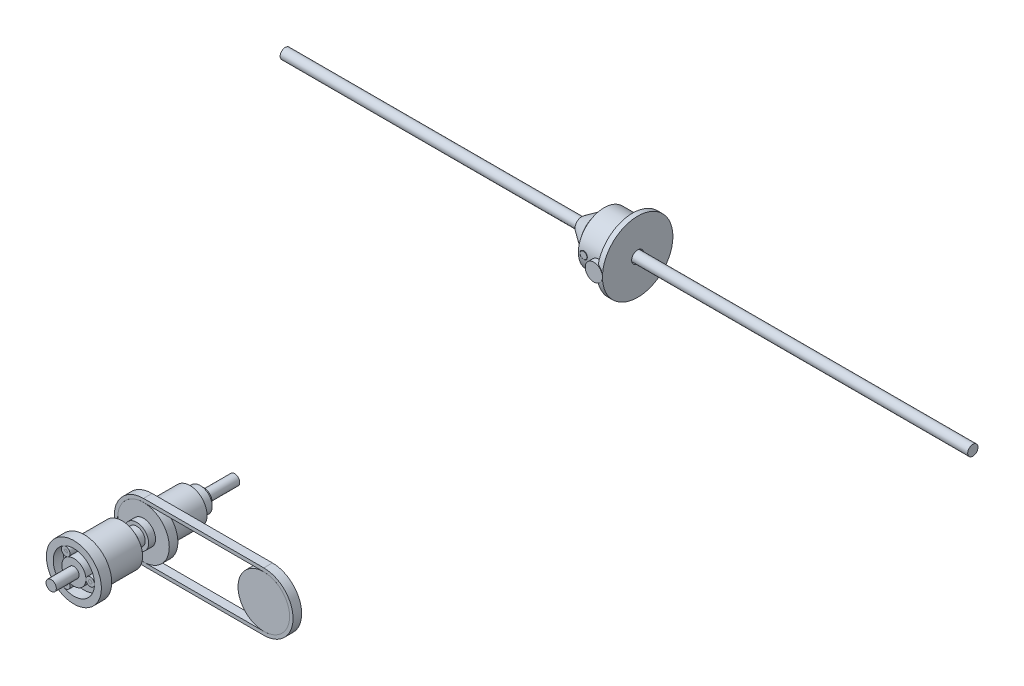
SolidWorks part; units mm, degrees
note: The reader was unsure of these and kept them because the rebuilt part matched: shared geometry of "Sketch14<2>", "Sketch32<3>", "Sketch50<2>", "Sketch52<2>".
other "RD S Gear Inner"
other "RD S Gear Outer"
other "RD L Gear Left"
other "RD L Gear Right"
other "RD Ring Gear"
other "RD Pinion"
other "RD S Gear Inner"
ref_plane "Front Plane" through (0, 0, 0) normal (0, 0, 1) x (1, 0, 0)
ref_plane "Top Plane" through (0, 0, 0) normal (0, 1, 0) x (1, 0, 0)
ref_plane "Right Plane" through (0, 0, 0) normal (1, 0, 0) x (0, 0, -1)
sketch "Top View Layout" plane through (0, 0, 0) normal (0, 1, 0) x (1, 0, 0)
  line L0 (-100, 125) -> (100, 125)
  line L1 (0, 125) -> (0, -125)
  line L2 (-100, -125) -> (100, -125)
  line L3 (0, -15) -> (35, -15) construction
  line L4 (35, -15) -> (35, -125) construction
  line L5 (2.5, 114.75) -> (2.5, 135.25) construction
  line L6 (-2.5, 114.75) -> (2.5, 114.75) construction
  line L7 (-8.75, 127) -> (-2.75, 127) construction
  line L8 (-2.5, 114.75) -> (2.5, 114.75) construction
  line L9 (-2.5, 114.75) -> (-2.5, 116.25) construction
  line L10 (-2.5, 116.25) -> (2.5, 116.25) construction
  line L11 (2.5, 114.75) -> (2.5, 116.25) construction
  line L12 (2.5, 135.25) -> (1, 135.25) construction
  line L13 (2.5, 135.25) -> (2.5, 114.75) construction
  line L14 (2.5, 114.75) -> (1, 114.75) construction
  line L15 (1, 135.25) -> (1, 114.75) construction
  line L16 (-4.25, 128.5) -> (-2.75, 128.5) construction
  line L17 (-4.25, 128.5) -> (-4.25, 121.5) construction
  line L18 (-4.25, 121.5) -> (-2.75, 121.5) construction
  line L19 (-2.75, 128.5) -> (-2.75, 121.5) construction
  line L20 (-4.25, 128.5) -> (-2.75, 121.5) construction
  line L21 (-4.25, 121.5) -> (-2.75, 128.5) construction
  line L22 (-8.75, 128.5) -> (-7.25, 128.5) construction
  line L23 (-8.75, 128.5) -> (-8.75, 121.5) construction
  line L24 (-8.75, 121.5) -> (-7.25, 121.5) construction
  line L25 (-7.25, 128.5) -> (-7.25, 121.5) construction
  line L26 (-8.75, 128.5) -> (-7.25, 121.5) construction
  line L27 (-8.75, 121.5) -> (-7.25, 128.5) construction
  line L28 (-8.75, 123) -> (-2.75, 123) construction
  line L29 (-5.75, 123) -> (-5.75, 120.2863) construction
  line L30 (-5.75, 127) -> (-5.75, 129.2691) construction
  point P8 (0, 114.75)
  point P9 (0, 0)
  point P11 (2.5, 125)
  point P16 (2.5, 125)
  point P19 (0, 114.75)
  point P23 (-3.5, 125)
  point P28 (-8, 125)
  dimension "D1" = 250
  dimension "D2" = 200
  dimension "D3" = 35
  dimension "D4" = 15
  dimension "D5" = 5
  dimension "D6" = 20.5
  dimension "D7" = 1.5
  dimension "D8" = 1.5
  dimension "D9" = 1.5
  dimension "D10" = 7
  dimension "D11" = 3.5
  dimension "D12" = 8
  dimension "D13" = 1.5
  dimension "D14" = 1.5
ref_plane "Left" through (100, 0, 0) normal (-1, 0, 0) x (0, 0, 1)
ref_plane "Right" through (-100, 0, 0) normal (-1, 0, 0) x (0, 0, 1)
sketch "Left Wheels" plane through (100, 0, 0) normal (-1, 0, 0) x (0, 0, 1)
  circle A0 centre (125, 0) radius 25
  circle A1 centre (-125, 0) radius 25
  dimension "D1" = 50
  dimension "D2" = 50
sketch "Right Wheels" plane through (-100, 0, 0) normal (-1, 0, 0) x (0, 0, 1)
  circle A0 centre (-125, 0) radius 25 construction
  circle A1 centre (125, 0) radius 25 construction
  circle A2 centre (-125, 0) radius 25
  circle A3 centre (125, 0) radius 25
ref_plane "Rear Differential Pinion Plane" through (0, 0, -114.75) normal (0, 0, 1) x (1, 0, 0)
sketch "Rear Differential Pinion Profile" plane through (0, 0, -114.75) normal (0, 0, 1) x (1, 0, 0)
  circle A0 centre (0, 0) radius 2.5
ref_plane "Rear Differential Ring Gear Plane" through (2.5, 0, 0) normal (1, 0, 0) x (0, 0, -1)
ref_plane "Rear Axle" through (0, 0, -125) normal (0, 0, 1) x (1, 0, 0)
sketch "Rear Differential Ring Gear Profile" plane through (2.5, 0, 0) normal (1, 0, 0) x (0, 0, -1)
  line L0 (114.75, 0) -> (135.25, 0) construction
  circle A0 centre (125, 0) radius 10.25
extrude "Rear Differential Pinion" add sketch "Rear Differential Pinion Profile" against normal blind 1.5 contours A0
extrude "Rear Differential Ring Gear" add sketch "Rear Differential Ring Gear Profile" against normal blind 1.5 separate body contours A0
ref_plane "RD Inner L Gear Plane" through (-2.75, 0, 0) normal (1, 0, 0) x (0, 0, -1)
ref_plane "RD Outer L Gear Plane" through (-8.75, 0, 0) normal (1, 0, 0) x (0, 0, -1)
sketch "RD Inner L Gear Profile" plane through (-2.75, 0, 0) normal (1, 0, 0) x (0, 0, -1)
  circle A0 centre (125, 0) radius 3.5
sketch "RD Outer L Gear Profile" plane through (-8.75, 0, 0) normal (1, 0, 0) x (0, 0, -1)
  line L0 (128.5, 0) -> (121.5, 0) construction
  circle A0 centre (125, 0) radius 3.5
ref_plane "RD Inner S Gear Plane" through (0, 0, -121.5) normal (0, 0, 1) x (1, 0, 0)
ref_plane "RD Outer S Gear Plane" through (0, 0, -128.5) normal (0, 0, 1) x (1, 0, 0)
sketch "RD Inner S Gear Profile" plane through (0, 0, -121.5) normal (0, 0, 1) x (1, 0, 0)
  line L0 (-8.75, 0) -> (-7.25, 0) construction
  circle A0 centre (-5.75, 0) radius 3
sketch "RD Outer S Gear Profile" plane through (0, 0, -128.5) normal (0, 0, 1) x (1, 0, 0)
  line L0 (-8.75, 0) -> (-7.25, 0) construction
  circle A2 centre (-5.75, 0) radius 3
extrude "RD Outer L Gear Extrude" add sketch "RD Outer L Gear Profile" along normal blind 1.5 separate body contours A0
extrude "RD Inner L Gear Extrude" add sketch "RD Inner L Gear Profile" against normal blind 1.5 separate body contours A0
extrude "RD Outer S Gear Extrude" add sketch "RD Outer S Gear Profile" along normal blind 1.5 separate body contours A2
extrude "RD Inner S Gear Extrude" add sketch "RD Inner S Gear Profile" against normal blind 1.5 separate body contours A0
sketch "RD Ring Gear Case Profile" plane through (1, 0, 0) normal (-1, 0, 0) x (0, 0, 1)
  line L0 (-121.5, 3.2113) -> (-121.5, -3.2113)
  line L1 (-128.5, 3.2113) -> (-128.5, -3.2113)
  line L2 (-121.5, 6.6332) -> (-121.5, 3.2113) construction
  line L3 (-128.5, 6.6332) -> (-128.5, 3.2113) construction
  line L4 (-121.5, -3.2113) -> (-121.5, -6.6332) construction
  line L5 (-128.5, -3.2113) -> (-128.5, -6.6332) construction
  circle A0 centre (-125, 0) radius 7.5
  arc A1 (-121.5, 3.2113) -> (-128.5, 3.2113) centre (-125, 0) ccw
  arc A2 (-121.5, -3.2113) -> (-121.5, 3.2113) centre (-125, 0) ccw construction
  arc A3 (-128.5, 3.2113) -> (-128.5, -3.2113) centre (-125, 0) ccw construction
  arc A4 (-128.5, -3.2113) -> (-121.5, -3.2113) centre (-125, 0) ccw
  point P7 (-121.5, 0)
  dimension "D1" = 15
  dimension "D2" = 9.5
extrude "RD Ring Gear Case " add sketch "RD Ring Gear Case Profile" along normal blind 8.25
sketch "Sketch11" plane through (-7.25, 0, 0) normal (-1, 0, 0) x (0, 0, 1)
  circle A0 centre (-125, 0) radius 5.5
  circle A1 centre (-125, 0) radius 4.75
  arc A2 (-121.5, 3.2113) -> (-128.5, 3.2113) centre (-125, 0) ccw construction
  dimension "D1" = 11
extrude "Boss-Extrude8" add sketch "Sketch11" along normal up to vertex (1.5 mm away) up to point (-8.75, 0, -128.5)
fillet "Fillet1" radius 2 1 edges at (-7.25, 0, -119.5)
sketch "Sketch12" plane through (0, 0, -125) normal (0, 0, 1) x (1, 0, 0)
  line L0 (-8.75, 0) -> (-13.75, 0) construction
  line L1 (-8.75, 0) -> (-7.25, 0) construction
  line L2 (-8.75, 0) -> (-7.25, 0) construction
  line L3 (-100, 0) -> (100, 0) construction
  line L4 (-100, 0) -> (100, 0) construction
  line L5 (-8.75, 5.5) -> (-8.75, -5.5) construction
  line L6 (-13.75, 0) -> (-13.75, 2)
  line L7 (-13.75, 2) -> (-8.75, 5.5)
  line L8 (-13.75, 0) -> (-8.75, 0)
  line L9 (-8.75, 0) -> (-8.75, 5.5)
  point P15 (-13.75, 1)
  dimension "D1" = 5
  dimension "D2" = 2
revolve "Revolve1" add sketch "Sketch12" angle 360 about L0
sketch "Sketch13" plane through (2.5, 0, 0) normal (1, 0, 0) x (0, 0, -1)
  circle A0 centre (125, 0) radius 1.75
  dimension "D1" = 3.5
extrude "Cut-Extrude1" cut sketch "Sketch13" against normal through all
sketch "Sketch14" plane through (0, 0, -121.5) normal (0, 0, 1) x (1, 0, 0)
  circle A0 centre (-5.75, 0) radius 1
  dimension "D1" = 2
extrude "Boss-Extrude9" add sketch "Sketch14" along normal blind 4
sketch "Sketch15" plane through (0, 0, -121.5) normal (0, 0, 1) x (1, 0, 0)
  circle A0 centre (-5.75, 0) radius 1.1
  dimension "D1" = 2.2
extrude "Cut-Extrude2" cut sketch "Sketch15" against normal through all both and the other way through all
extrude "Boss-Extrude10" add sketch "Sketch14<2>" against normal blind 4 from surface at -7 starting at face at (-2.75, 0, -128.5)
sketch "Sketch14<2>" plane through (0, 0, -121.5) normal (0, 0, 1) x (1, 0, 0) same geometry as "Sketch14"
sketch "Sketch16" plane through (-8.75, 0, 0) normal (-1, 0, 0) x (0, 0, 1)
  circle A0 centre (-125, 0) radius 1.5
  dimension "D1" = 3
extrude "Boss-Extrude11" add sketch "Sketch16" along normal up to vertex (91.25 mm away) up to point (-100, 0, -125)
sketch "Sketch17" plane through (-2.75, 0, 0) normal (1, 0, 0) x (0, 0, -1)
  circle A0 centre (125, 0) radius 1.5 construction
  circle A1 centre (125, 0) radius 1.5
extrude "Boss-Extrude12" add sketch "Sketch17" along normal up to vertex (102.75 mm away) up to point (100, 0, -125)
sketch "Transfer Case Layout" plane through (0, 0, 0) normal (0, 1, 0) x (1, 0, 0)
  line L0 (0, 125) -> (0, -125) construction
  line L1 (-7.5, -13.75) -> (7.5, -13.75)
  line L2 (-7.5, -13.75) -> (-7.5, -16.25)
  line L3 (-7.5, -16.25) -> (7.5, -16.25)
  line L4 (7.5, -13.75) -> (7.5, -16.25)
  line L5 (-7.5, -13.75) -> (7.5, -16.25) construction
  line L6 (-7.5, -16.25) -> (7.5, -13.75) construction
  line L7 (27.5, -13.75) -> (42.5, -13.75)
  line L8 (27.5, -13.75) -> (27.5, -16.25)
  line L9 (27.5, -16.25) -> (42.5, -16.25)
  line L10 (42.5, -13.75) -> (42.5, -16.25)
  line L11 (27.5, -13.75) -> (42.5, -16.25) construction
  line L12 (27.5, -16.25) -> (42.5, -13.75) construction
  line L13 (2.5, -17.25) -> (-2.5, -17.25)
  line L14 (2.5, -17.25) -> (2.5, -16.25)
  line L15 (2.5, -16.25) -> (-2.5, -16.25)
  line L16 (-2.5, -17.25) -> (-2.5, -16.25)
  line L17 (2.5, -17.25) -> (-2.5, -16.25) construction
  line L18 (2.5, -16.25) -> (-2.5, -17.25) construction
  line L19 (-2, -4.75) -> (-2, -10.75)
  line L20 (3.5, -18.25) -> (-3.5, -18.25)
  line L21 (3.5, -18.25) -> (3.5, -16.25)
  line L22 (3.5, -16.25) -> (-3.5, -16.25)
  line L23 (-3.5, -18.25) -> (-3.5, -16.25)
  line L24 (3.5, -18.25) -> (-3.5, -16.25) construction
  line L25 (3.5, -16.25) -> (-3.5, -18.25) construction
  line L26 (2.5, -20) -> (-2.5, -20)
  line L27 (2.5, -20) -> (2.5, -17.5)
  line L28 (2.5, -17.5) -> (-2.5, -17.5)
  line L29 (-2.5, -20) -> (-2.5, -17.5)
  line L30 (2.5, -20) -> (-2.5, -17.5) construction
  line L31 (2.5, -17.5) -> (-2.5, -20) construction
  line L32 (-3.5, -9.25) -> (3.5, -9.25)
  line L33 (-3.5, -9.25) -> (-3.5, -10.75)
  line L34 (-3.5, -10.75) -> (3.5, -10.75)
  line L35 (3.5, -9.25) -> (3.5, -10.75)
  line L36 (-3.5, -9.25) -> (3.5, -10.75) construction
  line L37 (-3.5, -10.75) -> (3.5, -9.25) construction
  line L38 (-3.5, -4.75) -> (3.5, -4.75)
  line L39 (-3.5, -4.75) -> (-3.5, -6.25)
  line L40 (-3.5, -6.25) -> (3.5, -6.25)
  line L41 (3.5, -4.75) -> (3.5, -6.25)
  line L42 (-3.5, -4.75) -> (3.5, -6.25) construction
  line L43 (-3.5, -6.25) -> (3.5, -4.75) construction
  line L44 (2, -4.75) -> (2, -10.75)
  line L45 (0, -6.25) -> (0, -9.25) construction
  line L46 (-5, -2.75) -> (5, -2.75) construction
  line L47 (-5, -2.75) -> (-5, -12.75) construction
  line L48 (-5, -12.75) -> (5, -12.75) construction
  line L49 (5, -2.75) -> (5, -12.75) construction
  line L50 (-5, -2.75) -> (5, -12.75) construction
  line L51 (-5, -12.75) -> (5, -2.75) construction
  line L52 (-6, -22.5) -> (-6, -24)
  line L53 (-2.5, -1.75) -> (2.5, -1.75)
  line L54 (-2.5, -1.75) -> (-2.5, -2.75)
  line L55 (-2.5, -2.75) -> (2.5, -2.75)
  line L56 (2.5, -1.75) -> (2.5, -2.75)
  line L57 (-2.5, -1.75) -> (2.5, -2.75) construction
  line L58 (-2.5, -2.75) -> (2.5, -1.75) construction
  line L59 (-2.5, 1.25) -> (2.5, 1.25)
  line L60 (-2.5, 1.25) -> (-2.5, -0.75)
  line L61 (-2.5, -0.75) -> (2.5, -0.75)
  line L62 (2.5, 1.25) -> (2.5, -0.75)
  line L63 (-2.5, 1.25) -> (2.5, -0.75) construction
  line L64 (-2.5, -0.75) -> (2.5, 1.25) construction
  line L65 (3.5, 0.25) -> (-3.5, 0.25)
  line L66 (3.5, 0.25) -> (3.5, -2.25)
  line L67 (3.5, -2.25) -> (-3.5, -2.25)
  line L68 (-3.5, 0.25) -> (-3.5, -2.25)
  line L69 (3.5, 0.25) -> (-3.5, -2.25) construction
  line L70 (3.5, -2.25) -> (-3.5, 0.25) construction
  line L71 (-2.5, -22.5) -> (2.5, -22.5)
  line L72 (-2.5, -22.5) -> (-2.5, -27.5)
  line L73 (-2.5, -27.5) -> (2.5, -27.5)
  line L74 (2.5, -22.5) -> (2.5, -27.5)
  line L75 (-2.5, -22.5) -> (2.5, -27.5) construction
  line L76 (-2.5, -27.5) -> (2.5, -22.5) construction
  line L77 (-6, -24) -> (6, -24)
  line L78 (6, -24) -> (6, -22.5)
  line L79 (6, -22.5) -> (-6, -22.5)
  line L80 (-4.5, -22.5) -> (-4.5, -24)
  line L81 (4.5, -22.5) -> (4.5, -24)
  line L82 (-6, -24) -> (-6, -33.5) construction
  line L83 (2.5, -29.5) -> (-2.5, -29.5)
  line L84 (2.5, -29.5) -> (2.5, -28)
  line L85 (2.5, -28) -> (-2.5, -28)
  line L86 (-2.5, -29.5) -> (-2.5, -28)
  line L87 (2.5, -29.5) -> (-2.5, -28) construction
  line L88 (2.5, -28) -> (-2.5, -29.5) construction
  line L89 (-4.5, -26.5) -> (4.5, -26.5)
  line L90 (-4.5, -26.5) -> (-4.5, -29.5)
  line L91 (-4.5, -29.5) -> (4.5, -29.5)
  line L92 (4.5, -26.5) -> (4.5, -29.5)
  line L93 (-4.5, -26.5) -> (4.5, -29.5) construction
  line L94 (-4.5, -29.5) -> (4.5, -26.5) construction
  line L95 (6, -24) -> (6, -33.5) construction
  line L96 (-3.5, -33.5) -> (-3.5, -36.5)
  line L97 (6, -36.5) -> (-6, -36.5)
  line L98 (6, -36.5) -> (6, -33.5)
  line L99 (6, -33.5) -> (-6, -33.5)
  line L100 (-6, -36.5) -> (-6, -33.5)
  line L101 (6, -36.5) -> (-6, -33.5) construction
  line L102 (6, -33.5) -> (-6, -36.5) construction
  line L103 (3.5, -33.5) -> (3.5, -36.5)
  line L104 (0, -28) -> (0, -43.1129)
  line L109 (8, -36.5) -> (-8, -36.5)
  line L110 (8, -36.5) -> (8, -33.5)
  line L111 (8, -33.5) -> (-8, -33.5)
  line L112 (-8, -36.5) -> (-8, -33.5)
  line L113 (8, -36.5) -> (-8, -33.5) construction
  line L114 (8, -33.5) -> (-8, -36.5) construction
  line L115 (0, -27.5) -> (0, -9.25)
  line L116 (0, -6.25) -> (0, -1.75)
  line L117 (0, -0.75) -> (0, 11.0375)
  line L118 (35, -22.7597) -> (35, -7.2403)
  point P0 (0, -15)
  point P6 (35, -15)
  point P12 (0, -16.75)
  point P19 (0, -17.25)
  point P24 (0, -18.75)
  point P29 (0, -10)
  point P34 (0, -5.5)
  point P43 (0, -7.75)
  point P50 (0, -2.25)
  point P55 (0, 0.25)
  point P60 (0, -1)
  point P65 (0, -25)
  point P72 (0, -22.5)
  point P79 (0, -28.75)
  point P84 (0, -28)
  point P92 (0, -35)
  point P98 (0, -35)
  point P99 (0, -35)
  point P110 (0, 0)
  point P113 (35, -15)
  point P114 (0, 0)
  point P115 (0, 0)
  point P116 (0, 0)
  point P117 (0, 0)
  point P118 (0, 0)
  point P119 (0, 0)
  point P120 (0, 0)
  point P121 (0, 0)
  point P122 (0, 0)
  point P123 (0, 0)
  point P124 (0, 0)
  point P125 (0, 0)
  point P126 (6, -33.5)
  point P127 (0, 0)
  point P128 (0, 0)
  point P129 (0, 0)
  point P130 (0, 0)
  point P131 (0, 0)
  point P132 (0, 0)
  point P133 (2.5, -1.75)
  point P134 (0, 0)
  point P135 (0, 0)
  point P136 (0, 0)
  point P137 (0, 0)
  point P138 (0, 0)
  point P139 (0, 0)
  point P140 (0, 0)
  point P141 (0, 0)
  point P142 (0, 0)
  point P143 (0, 0)
  point P144 (0, 0)
  point P145 (0, 0)
  point P146 (0, 0)
  point P147 (0, 0)
  dimension "D1" = 2.5
  dimension "D2" = 2.5
  dimension "D3" = 15
  dimension "D4" = 15
  dimension "D5" = 1
  dimension "D6" = 5
  dimension "D7" = 7
  dimension "D8" = 2
  dimension "D9" = 0.25
  dimension "D10" = 2.5
  dimension "D11" = 7
  dimension "D12" = 5
  dimension "D13" = 1.5
  dimension "D14" = 1.5
  dimension "D15" = 1.5
  dimension "D16" = 1.5
  dimension "D17" = 6
  dimension "D18" = 2
  dimension "D19" = 1.5
  dimension "D20" = 5
  dimension "D21" = 1
  dimension "D22" = 2
  dimension "D23" = 1
  dimension "D24" = 7
  dimension "D25" = 2.5
  dimension "D26" = 0.5
  dimension "D27" = 5
  dimension "D28" = 5
  dimension "D29" = 10
  dimension "D30" = 1.5
  dimension "D31" = 12
  dimension "D32" = 1.5
  dimension "D33" = 1.5
  dimension "D34" = 1.5
  dimension "D35" = 0.5
  dimension "D36" = 3
  dimension "D37" = 3
  dimension "D38" = 20
  dimension "D39" = 2.5
  dimension "D40" = 2.5
  dimension "D41" = 7
  dimension "D42" = 2
  dimension "D43" = 16
sketch "Sketch18" plane through (0, 0, 0) normal (0, 1, 0) x (1, 0, 0)
  line L1 (-122.7566, 344.0522) -> (127.2434, 344.0522)
  line L2 (-122.7566, 344.0522) -> (-122.7566, -155.9478)
  line L3 (-122.7566, -155.9478) -> (127.2434, -155.9478)
  line L4 (127.2434, 344.0522) -> (127.2434, -155.9478)
  dimension "D1" = 250
  dimension "D2" = 500
surface "Surface-Extrude1" sketch "Sketch18" parameters "D1"=175, "D2"=25
ref_plane "FWD Sprocket Plane" through (0, 0, 15) normal (0, 0, 1) x (1, 0, 0)
sketch "Sketch19" plane through (0, 0, 15) normal (0, 0, 1) x (1, 0, 0)
  circle A0 centre (35, 0) radius 7.5
  circle A1 centre (0, 0) radius 7.5
  point P6 (7.5, 0)
  point P9 (27.5, 0)
extrude "FWD Sprockets" add sketch "Sketch19" along normal up to vertex (1.25 mm away) and the other way up to vertex (1.25 mm away) separate body up to point (-7.5, 0, 16.25) other way up to point (-7.5, 0, 13.75)
sketch "Sketch20" plane through (0, 0, 15) normal (0, 0, 1) x (1, 0, 0)
  line L0 (0, 8.5) -> (35, 8.5)
  line L1 (0, -8.5) -> (35, -8.5)
  line L2 (0, 7.5) -> (35, 7.5)
  line L3 (0, -7.5) -> (35, -7.5)
  circle A0 centre (0, 0) radius 7.5 construction
  arc A1 (0, 7.5) -> (0, -7.5) centre (0, 0) ccw
  circle A2 centre (35, 0) radius 7.5 construction
  arc A3 (35, -7.5) -> (35, 7.5) centre (35, 0) ccw
  arc A4 (0, 8.5) -> (0, -8.5) centre (0, 0) ccw
  arc A5 (35, -8.5) -> (35, 8.5) centre (35, 0) ccw
  arc A6 (4, -7.5) -> (4, 7.5) centre (0, 0) ccw construction
  arc A7 (0, -7.5) -> (0, 7.5) centre (0, 0) ccw construction
  arc A8 (35, 7.5) -> (35, -7.5) centre (35, 0) ccw construction
  arc A9 (31, 7.5) -> (31, -7.5) centre (35, 0) ccw construction
  arc A10 (4, 7.5) -> (0, 8.5) centre (0, 0) ccw construction
  arc A11 (35, 8.5) -> (31, 7.5) centre (35, 0) ccw construction
  arc A12 (31, -7.5) -> (35, -8.5) centre (35, 0) ccw construction
  arc A13 (0, -8.5) -> (4, -7.5) centre (0, 0) ccw construction
  dimension "D1" = 1
  dimension "D2" = 1
extrude "FWD Sprocket Chain" add sketch "Sketch20" along normal up to surface and the other way up to surface separate body up to face at (7.5, 0, 16.25) other way up to face at (7.5, 0, 13.75)
sketch "Sketch21" plane through (0, 0, 16.25) normal (0, 0, 1) x (1, 0, 0)
  circle A0 centre (0, 0) radius 2.5
  point P3 (2.5, 0)
extrude "Boss-Extrude15" add sketch "Sketch21" along normal up to vertex (1 mm away) up to point (-2.5, 0, 17.25)
ref_plane "Mode Sleeve Gear Plane" through (0, 0, 18.25) normal (0, 0, 1) x (1, 0, 0)
sketch "Sketch22" plane through (0, 0, 18.25) normal (0, 0, 1) x (1, 0, 0)
  circle A0 centre (0, 0) radius 3.5
  circle A1 centre (0, 0) radius 2.5 construction
  circle A2 centre (0, 0) radius 2.5
extrude "Mode Sleeve Gear" add sketch "Sketch22" against normal up to vertex (2 mm away) separate body up to point (3.5, 0, 16.25)
sketch "Sketch23" plane through (0, 0, 18.25) normal (0, 0, 1) x (1, 0, 0)
  circle A0 centre (0, 0) radius 2.5 construction
  circle A1 centre (0, 0) radius 2.5
extrude "Boss-Extrude17" add sketch "Sketch23" along normal up to vertex (1.75 mm away) separate body up to point (2.5, 0, 20)
ref_plane "Range Sleeve Rear Plane" through (0, 0, 22.5) normal (0, 0, 1) x (1, 0, 0)
sketch "Sketch24" plane through (0, 0, 22.5) normal (0, 0, 1) x (1, 0, 0)
  circle A0 centre (0, 0) radius 2.5
extrude "Main Shaft Range Sleeve Gear" add sketch "Sketch24" along normal up to vertex (5 mm away) separate body up to point (-2.5, 0, 27.5)
sketch "Sketch25" plane through (0, 0, 22.5) normal (0, 0, 1) x (1, 0, 0)
  circle A0 centre (0, 0) radius 6
  circle A3 centre (0, 0) radius 4.5
extrude "Carrier Range Sleeve Gear" add sketch "Sketch25" along normal up to vertex (1.5 mm away) separate body up to point (6, 0, 24)
ref_plane "Range Sleeve Input Shaft Side" through (0, 0, 29.5) normal (0, 0, 1) x (1, 0, 0)
sketch "Sketch27" plane through (0, 0, 29.5) normal (0, 0, 1) x (1, 0, 0)
  circle A0 centre (0, 0) radius 2.5
extrude "Input Range Sleeve Gear" add sketch "Sketch27" against normal up to vertex (1.5 mm away) separate body up to point (2.5, 0, 28)
sketch "Sketch28" plane through (0, 0, 29.5) normal (0, 0, 1) x (1, 0, 0)
  circle A0 centre (0, 0) radius 4.5
  circle A1 centre (0, 0) radius 2.5 construction
  circle A2 centre (0, 0) radius 2.5
extrude "Range Sleeve Sleeve Gear" add sketch "Sketch28" against normal up to vertex (3 mm away) separate body up to point (4.5, 0, 26.5)
ref_plane "Planetary Input Side Plane" through (0, 0, 36.5) normal (0, 0, 1) x (1, 0, 0)
sketch "Sketch29" plane through (0, 0, 36.5) normal (0, 0, 1) x (1, 0, 0)
  circle A0 centre (0, 0) radius 3.5
extrude "Planetary Sun Gear" add sketch "Sketch29" against normal up to vertex (3 mm away) separate body up to point (3.5, 0, 33.5)
sketch "Sketch30" plane through (0, 0, 36.5) normal (0, 0, 1) x (1, 0, 0)
  line L0 (6, 0) -> (-6, 0) construction
  circle A0 centre (4.75, 0) radius 1.25
  point P3 (0, 0)
extrude "Planetary Planet Gear" add sketch "Sketch30" against normal up to vertex (3 mm away) separate body up to point (6, 0, 33.5)
pattern_circular "Planetary Planet Gear x 3" count 3 over 360 about axis through (0, 0, 0) along (0, 0, 1) of bodies 132
sketch "Sketch31" plane through (0, 0, 36.5) normal (0, 0, 1) x (1, 0, 0)
  circle A0 centre (0, 0) radius 6
  circle A1 centre (0, 0) radius 8
extrude "Planetary Ring Gear" add sketch "Sketch31" against normal up to vertex (3 mm away) separate body up to point (8, 0, 33.5)
ref_plane "Planetary Rear Side Plane" through (0, 0, 33.5) normal (0, 0, 1) x (1, 0, 0)
sketch "Sketch32" plane through (0, 0, 33.5) normal (0, 0, 1) x (1, 0, 0)
  line L0 (3.5, 0) -> (6, 0) construction
  line L1 (0, 0) -> (4.75, 0) construction
  line L2 (0, 0) -> (-2.375, -4.1136) construction
  circle A0 centre (0, 0) radius 6
  circle A1 centre (4.75, 0) radius 0.5
  circle A2 centre (-2.375, -4.1136) radius 0.5
  circle A3 centre (-2.375, 4.1136) radius 0.5
  point P4 (4.75, 0)
  dimension "D1" = 1
  dimension "D3" = 120
  dimension "D4" = 4.75
  dimension "D2" = 3
extrude "Carrier" add sketch "Sketch32" against normal blind 1 separate body contours A3 | A0 A3 A2 A1 | A1 | A2
extrude "Carrier Shafts" add sketch "Sketch32<3>" along normal up to vertex (3 mm away) contours A1 | A2 | A3 up to point (-3.5, 0, 36.5)
sketch "Sketch32<3>" plane through (0, 0, 33.5) normal (0, 0, 1) x (1, 0, 0) same geometry as "Sketch32"
sketch "Sketch33" plane through (0, 0, 33.5) normal (0, 0, 1) x (1, 0, 0)
  circle A0 centre (0, 0) radius 6 construction
  circle A1 centre (0, 0) radius 6
  circle A2 centre (0, 0) radius 5.5
  dimension "D1" = 0.5
extrude "Carrier Range Sleeve Gear Connect" add sketch "Sketch33" against normal up to surface (9.5 mm away) up to face at (6, 0, 24)
ref_plane "Center Diff Main Shaft Sidegear Plane" through (0, 0, 10.75) normal (0, 0, 1) x (1, 0, 0)
sketch "Sketch34" plane through (0, 0, 10.75) normal (0, 0, 1) x (1, 0, 0)
  circle A0 centre (0, 0) radius 3.5
extrude "Center Diff Main Shaft Side Gear" add sketch "Sketch34" against normal up to vertex (1.5 mm away) separate body up to point (3.5, 0, 9.25)
ref_plane "Center Diff Rear Shaft Sidegear Plane" through (0, 0, 4.75) normal (0, 0, 1) x (1, 0, 0)
ref_plane "Center Diff Mid Plane" through (0, 0, 7.75) normal (0, 0, 1) x (1, 0, 0)
mirror "Center Diff Rear Shaft Side Gear" about plane through (0, 0, 7.75) normal (0, 0, 1) of bodies 139
ref_plane "Center Diff Right Pinion Inner Plane" through (-2, 0, 0) normal (-1, 0, 0) x (0, 0, 1)
sketch "Sketch35" plane through (-2, 0, 0) normal (-1, 0, 0) x (0, 0, 1)
  line L0 (4.75, 0) -> (10.75, 0) construction
  circle A0 centre (7.75, 0) radius 3
extrude "Center Diff Right Pinion" add sketch "Sketch35" along normal up to vertex (1.5 mm away) separate body up to point (-3.5, 0, 10.75)
ref_plane "Center Diff Left Side Pinion Inner Plane" through (2, 0, 0) normal (-1, 0, 0) x (0, 0, 1)
sketch "Sketch36" plane through (2, 0, 0) normal (-1, 0, 0) x (0, 0, 1)
  line L0 (4.75, 0) -> (10.75, 0) construction
  circle A0 centre (7.75, 0) radius 3
extrude "Center Diff Left Pinion" add sketch "Sketch36" against normal up to vertex (1.5 mm away) separate body up to point (3.5, 0, 4.75)
ref_plane "Center Diff Rear Shaft Side Plane" through (0, 0, 2.75) normal (0, 0, 1) x (1, 0, 0)
sketch "Sketch37" plane through (0, 0, 2.75) normal (0, 0, 1) x (1, 0, 0)
  circle A0 centre (0, 0) radius 5
extrude "Center Diff Rear Axle Side Plate" add sketch "Sketch37" along normal up to vertex (2 mm away) separate body up to point (3.5, 0, 4.75)
mirror "Center Diff Main Shaft Side Plate" about plane through (0, 0, 7.75) normal (0, 0, 1) of bodies 143
sketch "Sketch38" plane through (0, 0, 2.75) normal (0, 0, 1) x (1, 0, 0)
  line L0 (3.5, -2.8284) -> (3.5, 2.8284)
  line L1 (-3.4263, -2.9173) -> (-3.5, -2.8284)
  line L2 (-3.5, -2.8284) -> (-3.5, 2.8284)
  circle A0 centre (0, 0) radius 5 construction
  circle A1 centre (0, 0) radius 5
  arc A2 (3.5, 2.8284) -> (-3.5, 2.8284) centre (0, 0) ccw
  arc A3 (3.5, -2.8284) -> (3.5, 2.8284) centre (0, 0) ccw construction
  arc A4 (-3.5, 2.8284) -> (-3.5, -2.8284) centre (0, 0) ccw construction
  arc A5 (-3.5, -2.8284) -> (3.5, -2.8284) centre (0, 0) ccw
  dimension "D1" = 0.5
extrude "Center Diff Case" add sketch "Sketch38" along normal up to surface (8 mm away) contours A1 A5 L2 A2 L0 up to face at (5, 0, 10.75)
sketch "Sketch39" plane through (0, 0, 2.75) normal (0, 0, 1) x (1, 0, 0)
  circle A0 centre (0, 0) radius 2.5
extrude "Center Diff Lock Gear" add sketch "Sketch39" against normal up to vertex (1 mm away) up to point (2.5, 0, 1.75)
ref_plane "Lock Sleeve Plane" through (0, 0, -0.25) normal (0, 0, 1) x (1, 0, 0)
sketch "Sketch41" plane through (0, 0, -0.25) normal (0, 0, 1) x (1, 0, 0)
  circle A0 centre (0, 0) radius 3.5
  circle A1 centre (0, 0) radius 2.5 construction
  circle A2 centre (0, 0) radius 2.5
extrude "Lock Sleeve" add sketch "Sketch41" along normal up to vertex (2.5 mm away) separate body up to point (-3.5, 0, 2.25)
sketch "Sketch42" plane through (0, 0, -0.25) normal (0, 0, 1) x (1, 0, 0)
  circle A0 centre (0, 0) radius 2.5 construction
  circle A1 centre (0, 0) radius 2.5
extrude "Lock Sleeve Rear Shaft Gear" add sketch "Sketch42" along normal up to vertex (1 mm away) and the other way up to vertex (1 mm away) separate body up to point (2.5, 0, 0.75) other way up to point (2.5, 0, -1.25)
sketch "Sketch43" plane through (-2, 0, 0) normal (-1, 0, 0) x (0, 0, 1)
  line L0 (4.75, 0) -> (10.75, 0) construction
  circle A0 centre (7.75, 0) radius 0.5
  dimension "D1" = 1
extrude "Center Diff Pinion Rotation Point Cut" cut sketch "Sketch43" against normal through all both and the other way through all
sketch "Sketch45" plane through (0, 0, 2.75) normal (0, 0, 1) x (1, 0, 0)
  circle A0 centre (0, 0) radius 0.5
  dimension "D1" = 1
extrude "Center Diff Side Gear Rotation Point" cut sketch "Sketch45" against normal through all both and the other way through all
sketch "Sketch46" plane through (0, 0, -0.25) normal (0, 0, 1) x (1, 0, 0)
  circle A0 centre (0, 0) radius 1.5
  dimension "D1" = 3
extrude "Rear Shaft" add sketch "Sketch46" along normal up to vertex (1 mm away) and the other way blind 10 up to point (0, 0, 0.75)
sketch "Sketch47" plane through (0, 0, 2.75) normal (0, 0, 1) x (1, 0, 0)
  circle A0 centre (0, 0) radius 0.5
  dimension "D1" = 1
extrude "Center Diff Rear Shaft Side Axle" add sketch "Sketch47" along normal up to vertex (3.5 mm away) and the other way up to vertex (1 mm away) up to point (0, 0, 6.25) other way up to point (0, 0, 1.75)
sketch "Sketch48" plane through (-2, 0, 0) normal (-1, 0, 0) x (0, 0, 1)
  circle A0 centre (7.75, 0) radius 0.5 construction
  circle A1 centre (7.75, 0) radius 0.5
extrude "Center Diff Right Side Pinion Axle" add sketch "Sketch48" along normal up to vertex (3 mm away) up to point (-5, 0, 12.75)
sketch "Sketch49" plane through (2, 0, 0) normal (-1, 0, 0) x (0, 0, 1)
  circle A0 centre (7.75, 0) radius 0.5 construction
  circle A1 centre (7.75, 0) radius 0.5
extrude "Center Diff Left Side Pinion Axle" add sketch "Sketch49" against normal up to vertex (3 mm away) up to point (5, 0, 2.75)
sketch "Sketch50" plane through (0, 0, 18.25) normal (0, 0, 1) x (1, 0, 0)
  circle A0 centre (0, 0) radius 0.5
  dimension "D1" = 1
extrude "Main Shaft Sprocket Rotation Point Cut" cut sketch "Sketch50" against normal through all both and the other way through all
extrude "Main Shaft" add sketch "Sketch50<2>" against normal up to vertex (9 mm away) and the other way up to vertex (9.25 mm away) up to point (0, 0, 9.25) other way up to point (0, 0, 27.5)
sketch "Sketch50<2>" plane through (0, 0, 18.25) normal (0, 0, 1) x (1, 0, 0) same geometry as "Sketch50"
sketch "Sketch52" plane through (0, 0, 36.5) normal (0, 0, 1) x (1, 0, 0)
  circle A0 centre (0, 0) radius 1.5
  dimension "D1" = 3
extrude "Input Shaft Carrier Cut" cut sketch "Sketch52" against normal through all both and the other way through all
extrude "Input Shaft" add sketch "Sketch52<2>" along normal up to vertex (6.6129 mm away) and the other way up to vertex (8.5 mm away) up to point (0, 0, 43.1129) other way up to point (0, 0, 28)
sketch "Sketch52<2>" plane through (0, 0, 36.5) normal (0, 0, 1) x (1, 0, 0) same geometry as "Sketch52"
